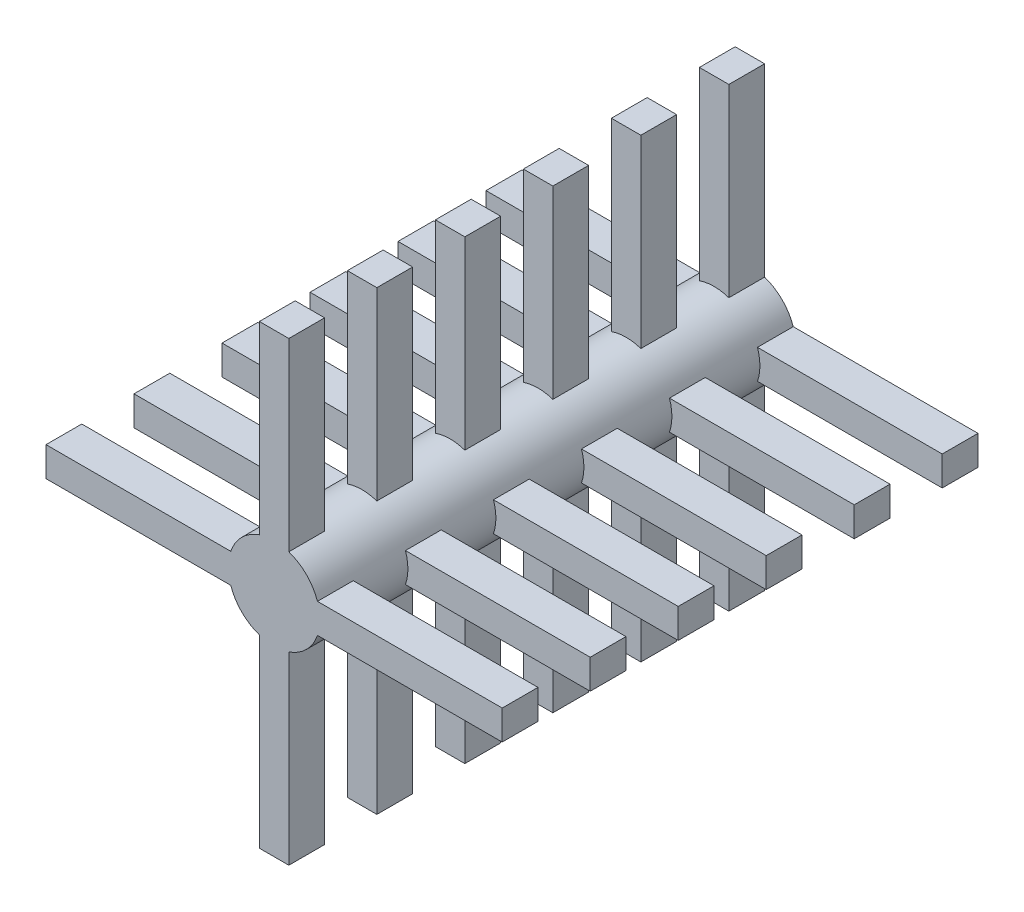
SolidWorks part; units mm, degrees
ref_plane "Front Plane" through (0, 0, 0) normal (0, 0, 1) x (1, 0, 0)
ref_plane "Top Plane" through (0, 0, 0) normal (0, 1, 0) x (1, 0, 0)
ref_plane "Right Plane" through (0, 0, 0) normal (1, 0, 0) x (0, 0, -1)
sketch "Sketch1" plane through (0, 0, 0) normal (0, 0, 1) x (1, 0, 0)
  line L0 (4.1185, 12.1159) -> (4.1185, 63.7634)
  line L1 (-4.1185, -63.7634) -> (4.1185, -63.7634)
  line L2 (-4.1185, -63.7634) -> (-4.1185, -12.1159)
  line L3 (-4.1185, 63.7634) -> (4.1185, 63.7634)
  line L4 (4.1185, -63.7634) -> (4.1185, -12.1159)
  line L5 (12.1159, -4.1185) -> (63.7634, -4.1185)
  line L6 (63.7634, 4.1185) -> (63.7634, -4.1185)
  line L7 (12.1159, 4.1185) -> (63.7634, 4.1185)
  line L8 (-4.1185, -12.1159) -> (-4.1185, -63.7634)
  line L9 (-4.1185, 12.1159) -> (-4.1185, 63.7634)
  line L10 (4.1185, -63.7634) -> (-4.1185, -63.7634)
  line L11 (4.1185, -12.1159) -> (4.1185, -63.7634)
  line L12 (-12.1159, 4.1185) -> (-63.7634, 4.1185)
  line L13 (-63.7634, -4.1185) -> (-63.7634, 4.1185)
  line L14 (-12.1159, -4.1185) -> (-63.7634, -4.1185)
  arc A0 (4.1185, -12.1159) -> (12.1159, -4.1185) centre (0, 0) ccw
  arc A1 (-4.1185, 12.1159) -> (-12.1159, 4.1185) centre (0, 0) ccw
  arc A2 (-12.1159, -4.1185) -> (-4.1185, -12.1159) centre (0, 0) ccw
  arc A3 (12.1159, 4.1185) -> (4.1185, 12.1159) centre (0, 0) ccw
  circle A4 centre (0, 0) radius 12.7968
  point P25 (0, 0)
  dimension "D1" = 4
extrude "Boss-Extrude1" add sketch "Sketch1" along normal blind 133 contours A3 A4 A1 A2 A0 region at (0, 0, 0)
extrude "Boss-Extrude2" add sketch "Sketch1<3>" along normal blind 10 contours A4 L0 L3 L9 | A4 L5 L6 L7 | A4 L2 L1 L4 | A4 L12 L13 L14 region at (0, 38.1675, 0) region at (38.1675, 0, 0) region at (-38.1675, 0, 0) region at (0, -38.1675, 0)
sketch "Sketch1<3>" plane through (0, 0, 0) normal (0, 0, 1) x (1, 0, 0) same geometry as "Sketch1"
pattern_linear "LPattern1" count 6 spacing 24.6 along (0, 0, 1) of "Boss-Extrude2"
